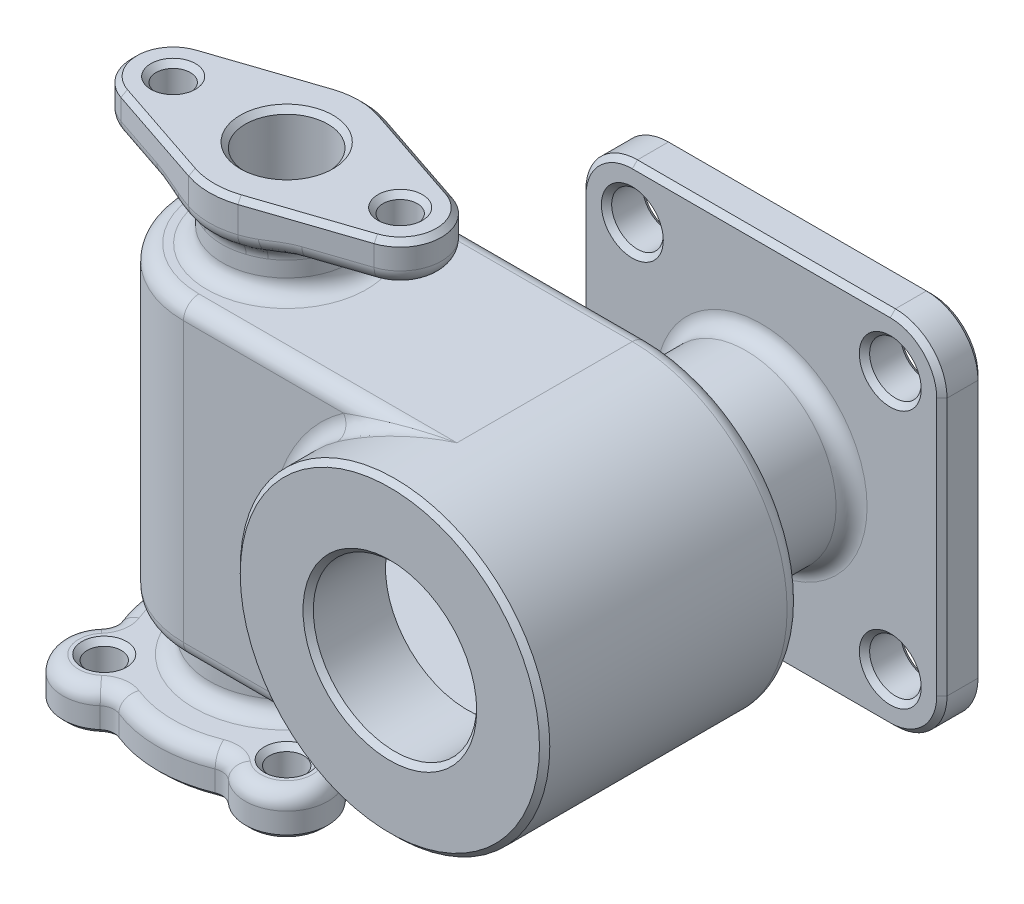
SolidWorks part; units mm, degrees
ref_plane "前视基准面" through (0, 0, 0) normal (0, 0, 1) x (1, 0, 0)
ref_plane "上视基准面" through (0, 0, 0) normal (0, 1, 0) x (1, 0, 0)
ref_plane "右视基准面" through (0, 0, 0) normal (1, 0, 0) x (0, 0, -1)
other "Configuration Table"
sketch3d "3D草图1"
  line L0 (0, 0, 0) -> (0, 0, 10)
ref_plane "基准面1" through (0, 0, 0) normal (0, 0, 1) x (1, 0, 0)
sketch "草图1" plane through (0, 0, 0) normal (0, 0, 1) x (1, 0, 0)
  line L0 (25, 35) -> (-25, 35)
  line L1 (-35, 25) -> (-35, -25)
  line L2 (-25, -35) -> (25, -35)
  line L3 (35, -25) -> (35, 25)
  arc A0 (35, 25) -> (25, 35) centre (25, 25) ccw
  arc A1 (-25, 35) -> (-35, 25) centre (-25, 25) ccw
  arc A2 (-35, -25) -> (-25, -35) centre (-25, -25) ccw
  arc A3 (25, -35) -> (35, -25) centre (25, -25) ccw
extrude "凸台-拉伸1" add sketch "草图1" along normal blind 8
sketch3d "3D草图2"
  line L0 (0, 0, 8) -> (0, 0, 18)
ref_plane "基准面2" through (0, 0, 8) normal (0, 0, 1) x (1, 0, 0)
sketch "草图2" plane through (0, 0, 8) normal (0, 0, 1) x (1, 0, 0)
  arc A0 (17.5, 0) -> (-17.5, 0) centre (0, 0) ccw
  arc A1 (-17.5, 0) -> (17.5, 0) centre (0, 0) ccw
extrude "凸台-拉伸2" add sketch "草图2" along normal blind 22
sketch3d "3D草图3"
  line L0 (0, 0, 30) -> (0, 0, 40)
ref_plane "基准面3" through (0, 0, 30) normal (0, 0, 1) x (1, 0, 0)
sketch "草图3" plane through (0, 0, 30) normal (0, 0, 1) x (1, 0, 0)
  arc A0 (30, 0) -> (-30, 0) centre (0, 0) ccw
  arc A1 (-30, 0) -> (30, 0) centre (0, 0) ccw
extrude "凸台-拉伸3" add sketch "草图3" along normal blind 50
sketch3d "3D草图4"
  line L0 (0, 0, 0) -> (0, -10, 0)
ref_plane "基准面4" through (0, 0, 0) normal (0, -1, 0) x (-1, 0, 0)
sketch "草图4" plane through (0, 0, 0) normal (0, -1, 0) x (-1, 0, 0)
  line L0 (0, -70) -> (50, -70)
  line L1 (50, -30) -> (0, -30)
  line L2 (0, -30) -> (0, -70)
  arc A0 (50, -70) -> (50, -30) centre (50, -50) ccw
extrude "凸台-拉伸4" add sketch "草图4" along normal mid plane 60
fillet "圆角1" radius 3 10 edges at (-25, 30, 70) (-70, 30, 50) (-25, 30, 30) (-25, -30, 70) (-70, -30, 50) (-25, -30, 30) (30, 0, 30) (17.5, 0, 30) (17.5, 0, 8) (-30, 0, 70) tangent propagation no
sketch3d "3D草图5"
  line L0 (-50, 30, 50) -> (-50, 40, 50)
ref_plane "基准面5" through (-50, 30, 50) normal (0, 1, 0) x (1, 0, 0)
sketch "草图5" plane through (-50, 30, 50) normal (0, 1, 0) x (1, 0, 0)
  arc A0 (12.5, 0) -> (-12.5, 0) centre (0, 0) ccw
  arc A1 (-12.5, 0) -> (12.5, 0) centre (0, 0) ccw
extrude "凸台-拉伸5" add sketch "草图5" along normal blind 9
sketch3d "3D草图6"
  line L0 (-50, -30, 50) -> (-50, -40, 50)
ref_plane "基准面6" through (-50, -30, 50) normal (0, -1, 0) x (-1, 0, 0)
sketch "草图6" plane through (-50, -30, 50) normal (0, -1, 0) x (-1, 0, 0)
  arc A0 (-15, 0) -> (15, 0) centre (0, 0) ccw
  arc A1 (15, 0) -> (-15, 0) centre (0, 0) ccw
extrude "凸台-拉伸6" add sketch "草图6" along normal blind 9
sketch3d "3D草图7"
  line L0 (-50, 39, 50) -> (-50, 49, 50)
ref_plane "基准面7" through (-50, 39, 50) normal (0, 1, 0) x (1, 0, 0)
sketch "草图7" plane through (-50, 39, 50) normal (0, 1, 0) x (1, 0, 0)
  line L0 (-4.7727, 14.2204) -> (-24.5455, 7.5842)
  line L1 (-24.5455, -7.5842) -> (-4.7727, -14.2204)
  line L2 (4.7727, -14.2204) -> (24.5455, -7.5842)
  line L3 (24.5455, 7.5842) -> (4.7727, 14.2204)
  arc A0 (4.7727, 14.2204) -> (-4.7727, 14.2204) centre (0, 0) ccw
  arc A1 (-24.5455, 7.5842) -> (-24.5455, -7.5842) centre (-22, 0) ccw
  arc A2 (-4.7727, -14.2204) -> (4.7727, -14.2204) centre (0, 0) ccw
  arc A3 (24.5455, -7.5842) -> (24.5455, 7.5842) centre (22, 0) ccw
extrude "凸台-拉伸7" add sketch "草图7" along normal blind 8
sketch3d "3D草图8"
  line L0 (-50, -39, 50) -> (-50, -49, 50)
ref_plane "基准面8" through (-50, -39, 50) normal (0, -1, 0) x (-1, 0, 0)
sketch "草图8" plane through (-50, -39, 50) normal (0, -1, 0) x (-1, 0, 0)
  arc A0 (-23.1917, -9.3353) -> (-23.7118, -12.4252) centre (-25.9747, -10.4555) cw
  arc A1 (-23.7118, -12.4252) -> (-12.4252, -23.7118) centre (-17.6777, -17.6777) ccw
  arc A2 (-12.4252, -23.7118) -> (-9.3353, -23.1917) centre (-10.4555, -25.9747) cw
  arc A3 (-9.3353, -23.1917) -> (9.3353, -23.1917) centre (0, 0) ccw
  arc A4 (9.3353, -23.1917) -> (12.4252, -23.7118) centre (10.4555, -25.9747) cw
  arc A5 (12.4252, -23.7118) -> (23.7118, -12.4252) centre (17.6777, -17.6777) ccw
  arc A6 (23.7118, -12.4252) -> (23.1917, -9.3353) centre (25.9747, -10.4555) cw
  arc A7 (23.1917, -9.3353) -> (23.1917, 9.3353) centre (0, 0) ccw
  arc A8 (23.1917, 9.3353) -> (23.7118, 12.4252) centre (25.9747, 10.4555) cw
  arc A9 (23.7118, 12.4252) -> (12.4252, 23.7118) centre (17.6777, 17.6777) ccw
  arc A10 (12.4252, 23.7118) -> (9.3353, 23.1917) centre (10.4555, 25.9747) cw
  arc A11 (9.3353, 23.1917) -> (-9.3353, 23.1917) centre (0, 0) ccw
  arc A12 (-9.3353, 23.1917) -> (-12.4252, 23.7118) centre (-10.4555, 25.9747) cw
  arc A13 (-12.4252, 23.7118) -> (-23.7118, 12.4252) centre (-17.6777, 17.6777) ccw
  arc A14 (-23.7118, 12.4252) -> (-23.1917, 9.3353) centre (-25.9747, 10.4555) cw
  arc A15 (-23.1917, 9.3353) -> (-23.1917, -9.3353) centre (0, 0) ccw
extrude "凸台-拉伸8" add sketch "草图8" along normal blind 8
fillet "圆角2" radius 3 2 edges at (-50, -30, 35) (-50, 30, 37.5) tangent propagation no
sketch3d "3D草图9"
  line L0 (0, 0, 0) -> (0, -10, 0)
ref_plane "基准面9" through (0, 0, 0) normal (0, -1, 0) x (-1, 0, 0)
sketch "草图9" plane through (0, 0, 0) normal (0, -1, 0) x (-1, 0, 0)
  line L0 (0, -65) -> (50, -65)
  line L1 (38.6863, -39) -> (0, -39)
  line L2 (0, -39) -> (0, -65)
  arc A0 (50, -65) -> (40.5719, -38.3333) centre (50, -50) ccw
  arc A1 (40.5719, -38.3333) -> (38.6863, -39) centre (38.6863, -36) cw
extrude "切除-拉伸1" cut sketch "草图9" against normal mid plane 40
sketch3d "3D草图10"
  line L0 (0, 0, 52) -> (0, 0, 62)
ref_plane "基准面10" through (0, 0, 52) normal (0, 0, 1) x (1, 0, 0)
sketch "草图10" plane through (0, 0, 52) normal (0, 0, 1) x (1, 0, 0)
  line L0 (0, -20) -> (0, 20)
  arc A0 (0, 20) -> (0, -20) centre (0, 0) cw
extrude "切除-拉伸2" cut sketch "草图10" against normal mid plane 26
fillet "圆角3" radius 3 10 edges at (-39.6863, 20, 38.8284) (-64.1421, 20, 45) (-64.1421, -20, 45) (-39.6863, -20, 38.8284) (20, 0, 65) (20, 0, 39) (-25, -20, 65) (-19.3431, -20, 39) (-25, 20, 65) (-19.3431, 20, 39)
sketch3d "3D草图11"
  line L0 (0, 0, 19.5) -> (0, 0, 29.5)
ref_plane "基准面11" through (0, 0, 19.5) normal (0, 0, 1) x (1, 0, 0)
sketch "草图11" plane through (0, 0, 19.5) normal (0, 0, 1) x (1, 0, 0)
  arc A0 (12.5, 0) -> (-12.5, 0) centre (0, 0) ccw
  arc A1 (-12.5, 0) -> (12.5, 0) centre (0, 0) ccw
extrude "切除-拉伸3" cut sketch "草图11" against normal mid plane 39
sketch3d "3D草图12"
  line L0 (0, 0, 72.5) -> (0, 0, 82.5)
ref_plane "基准面12" through (0, 0, 72.5) normal (0, 0, 1) x (1, 0, 0)
sketch "草图12" plane through (0, 0, 72.5) normal (0, 0, 1) x (1, 0, 0)
  arc A0 (15.8349, 0) -> (-15.8349, 0) centre (0, 0) ccw
  arc A1 (-15.8349, 0) -> (15.8349, 0) centre (0, 0) ccw
extrude "切除-拉伸4" cut sketch "草图12" against normal mid plane 15
cosmetic thread "装饰螺纹线1" parameters "D1"=15, "D2"=36
sketch3d "3D草图13"
  line L0 (-50, 0, 50) -> (-50, -10, 50)
ref_plane "基准面13" through (-50, 0, 50) normal (0, -1, 0) x (-1, 0, 0)
sketch "草图13" plane through (-50, 0, 50) normal (0, -1, 0) x (-1, 0, 0)
  arc A0 (-8, 0) -> (8, 0) centre (0, 0) ccw
  arc A1 (8, 0) -> (-8, 0) centre (0, 0) ccw
extrude "切除-拉伸5" cut sketch "草图13" against normal mid plane 94
sketch3d "3D草图14"
  line L0 (0, 0, 4) -> (0, 0, 14)
ref_plane "基准面14" through (0, 0, 4) normal (0, 0, 1) x (1, 0, 0)
sketch "草图14" plane through (0, 0, 4) normal (0, 0, 1) x (1, 0, 0)
  arc A0 (-20, -25) -> (-30, -25) centre (-25, -25) ccw
  arc A1 (-30, -25) -> (-20, -25) centre (-25, -25) ccw
  arc A2 (-20, 25) -> (-30, 25) centre (-25, 25) ccw
  arc A3 (-30, 25) -> (-20, 25) centre (-25, 25) ccw
  arc A4 (30, -25) -> (20, -25) centre (25, -25) ccw
  arc A5 (20, -25) -> (30, -25) centre (25, -25) ccw
  arc A6 (30, 25) -> (20, 25) centre (25, 25) ccw
  arc A7 (20, 25) -> (30, 25) centre (25, 25) ccw
extrude "切除-拉伸6" cut sketch "草图14" against normal mid plane 8
sketch3d "3D草图15"
  line L0 (-50, 43, 50) -> (-50, 33, 50)
ref_plane "基准面15" through (-50, 43, 50) normal (0, -1, 0) x (-1, 0, 0)
sketch "草图15" plane through (-50, 43, 50) normal (0, -1, 0) x (-1, 0, 0)
  arc A0 (18.6766, 0) -> (25.3234, 0) centre (22, 0) ccw
  arc A1 (25.3234, 0) -> (18.6766, 0) centre (22, 0) ccw
  arc A2 (-25.3234, 0) -> (-18.6766, 0) centre (-22, 0) ccw
  arc A3 (-18.6766, 0) -> (-25.3234, 0) centre (-22, 0) ccw
extrude "切除-拉伸7" cut sketch "草图15" against normal mid plane 8
cosmetic thread "装饰螺纹线2" parameters "D1"=8, "D2"=8
cosmetic thread "装饰螺纹线3" parameters "D1"=8, "D2"=8
sketch3d "3D草图16"
  line L0 (-50, -43, 50) -> (-50, -53, 50)
ref_plane "基准面16" through (-50, -43, 50) normal (0, -1, 0) x (-1, 0, 0)
sketch "草图16" plane through (-50, -43, 50) normal (0, -1, 0) x (-1, 0, 0)
  arc A0 (-21.0011, -17.6777) -> (-14.3543, -17.6777) centre (-17.6777, -17.6777) ccw
  arc A1 (-14.3543, -17.6777) -> (-21.0011, -17.6777) centre (-17.6777, -17.6777) ccw
  arc A2 (14.3543, -17.6777) -> (21.0011, -17.6777) centre (17.6777, -17.6777) ccw
  arc A3 (21.0011, -17.6777) -> (14.3543, -17.6777) centre (17.6777, -17.6777) ccw
  arc A4 (14.3543, 17.6777) -> (21.0011, 17.6777) centre (17.6777, 17.6777) ccw
  arc A5 (21.0011, 17.6777) -> (14.3543, 17.6777) centre (17.6777, 17.6777) ccw
  arc A6 (-21.0011, 17.6777) -> (-14.3543, 17.6777) centre (-17.6777, 17.6777) ccw
  arc A7 (-14.3543, 17.6777) -> (-21.0011, 17.6777) centre (-17.6777, 17.6777) ccw
extrude "切除-拉伸8" cut sketch "草图16" against normal mid plane 8
cosmetic thread "装饰螺纹线4" parameters "D1"=8, "D2"=8
cosmetic thread "装饰螺纹线5" parameters "D1"=8, "D2"=8
cosmetic thread "装饰螺纹线6" parameters "D1"=8, "D2"=8
cosmetic thread "装饰螺纹线7" parameters "D1"=8, "D2"=8
chamfer "倒角1" distance 1 angle 45 24 edges at (-32.3223, -39, 28.9989) (-32.3223, -47, 28.9989) (-67.6777, -39, 28.9989) (-67.6777, -47, 28.9989) (-67.6777, -39, 64.3543) (-67.6777, -47, 64.3543) (-32.3223, -47, 64.3543) (-32.3223, -39, 64.3543) (-28, 47, 46.6766) (-28, 39, 46.6766) (-72, 39, 46.6766) (-72, 47, 46.6766) (30, 25, 0) (30, 25, 8) (30, -25, 0) (30, -25, 8) (-20, 25, 0) (-20, 25, 8) (-20, -25, 8) (-20, -25, 0) (-50, -47, 42) (-50, 47, 42) (15.8349, 0, 80) (12.5, 0, 0) tangent propagation no
fillet "圆角4" radius 3 1 edges at (-50, 39, 62.5) tangent propagation no
fillet "圆角5" radius 3 1 edges at (-50, -39, 35) tangent propagation no
fillet "圆角6" radius 3 16 edges at (-60.9535, -39, 26.9837) (-73.3345, -39, 26.6655) (-73.0163, -39, 39.0465) (-73.0163, -39, 60.9535) (-73.3345, -39, 73.3345) (-60.9535, -39, 73.0163) (-39.0465, -39, 73.0163) (-26.6655, -39, 73.3345) (-26.9837, -39, 60.9535) (-26.9837, -39, 39.0465) (-26.6655, -39, 26.6655) (-39.0465, -39, 26.9837) (-25, -39, 50) (-50, -39, 75) (-75, -39, 50) (-50, -39, 25)
fillet "圆角7" radius 3 12 edges at (-33.4898, 39, 60.2811) (-43.3762, 39, 63.5992) (-50, 39, 65) (-56.6238, 39, 63.5992) (-66.5102, 39, 60.2811) (-66.5102, 39, 39.7189) (-56.6238, 39, 36.4008) (-50, 39, 35) (-43.3762, 39, 36.4008) (-33.4898, 39, 39.7189) (-80, 39, 50) (-20, 39, 50)
chamfer "倒角2" distance 1 angle 45 41 edges at (-25, -47, 50) (-26.9837, -47, 60.9535) (-26.6655, -47, 73.3345) (-39.0465, -47, 73.0163) (-50, -47, 75) (-60.9535, -47, 73.0163) (-73.3345, -47, 73.3345) (-73.0163, -47, 60.9535) (-75, -47, 50) (-73.0163, -47, 39.0465) (-73.3345, -47, 26.6655) (-60.9535, -47, 26.9837) (-50, -47, 25) (-39.0465, -47, 26.9837) (-26.6655, -47, 26.6655) (-26.9837, -47, 39.0465) (-50, 47, 35) (-64.6591, 47, 39.0977) (-80, 47, 50) (-64.6591, 47, 60.9023) (-50, 47, 65) (-35.3409, 47, 60.9023) (-20, 47, 50) (-35.3409, 47, 39.0977) (30, 0, 80) (32.0711, 32.0711, 0) (0, 35, 0) (-32.0711, 32.0711, 0) (-35, 0, 0) (-32.0711, -32.0711, 0) (0, -35, 0) (32.0711, -32.0711, 0) (35, 0, 0) (32.0711, 32.0711, 8) (0, 35, 8) (-32.0711, 32.0711, 8) (-35, 0, 8) (-32.0711, -32.0711, 8) (0, -35, 8) (32.0711, -32.0711, 8) (35, 0, 8) tangent propagation no
